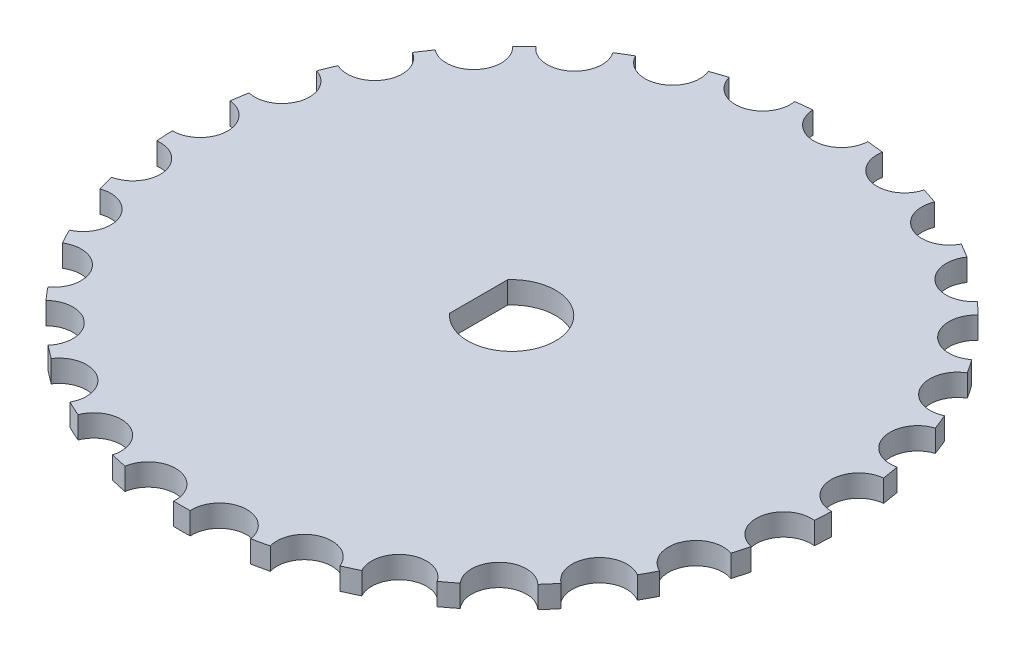
SolidWorks part; units mm, degrees
ref_plane "Front Plane" through (0, 0, 0) normal (0, 0, 1) x (1, 0, 0)
ref_plane "Top Plane" through (0, 0, 0) normal (0, 1, 0) x (1, 0, 0)
ref_plane "Right Plane" through (0, 0, 0) normal (1, 0, 0) x (0, 0, -1)
sketch "Sketch1" plane through (0, 0, 0) normal (0, 1, 0) x (1, 0, 0)
  circle A0 centre (0, 0) radius 30
  dimension "D1" = 60
extrude "Boss-Extrude1" add sketch "Sketch1" along normal blind 2
sketch "Sketch4" plane through (0, 2, 0) normal (0, 1, 0) x (1, 0, 0)
  line L0 (-3, -2.6458) -> (-3, 2.6458)
  arc A0 (-3, -2.6458) -> (-3, 2.6458) centre (0, 0) ccw
  dimension "D1" = 8
  dimension "D2" = 3
extrude "Cut-Extrude2" cut sketch "Sketch4" against normal through all
sketch "Sketch2" plane through (0, 2, 0) normal (0, 1, 0) x (1, 0, 0)
  circle A0 centre (0, 30) radius 2.5
  circle A1 centre (0, 0) radius 30 construction
  circle A2 centre (6.4491, 29.2986) radius 2.5
  circle A3 centre (12.5967, 27.2273) radius 2.5
  circle A4 centre (18.1552, 23.8828) radius 2.5
  circle A5 centre (22.8649, 19.4216) radius 2.5
  circle A6 centre (26.5054, 14.0523) radius 2.5
  circle A7 centre (28.9065, 8.0259) radius 2.5
  circle A8 centre (29.956, 1.6242) radius 2.5
  circle A9 centre (29.6048, -4.8535) radius 2.5
  circle A10 centre (27.8693, -11.1041) radius 2.5
  circle A11 centre (24.8307, -16.8356) radius 2.5
  circle A12 centre (20.631, -21.7799) radius 2.5
  circle A13 centre (15.4666, -25.7057) radius 2.5
  circle A14 centre (9.579, -28.4296) radius 2.5
  circle A15 centre (3.2436, -29.8241) radius 2.5
  circle A16 centre (-3.2436, -29.8241) radius 2.5
  circle A17 centre (-9.579, -28.4296) radius 2.5
  circle A18 centre (-15.4666, -25.7057) radius 2.5
  circle A19 centre (-20.631, -21.7799) radius 2.5
  circle A20 centre (-24.8307, -16.8356) radius 2.5
  circle A21 centre (-27.8693, -11.1041) radius 2.5
  circle A22 centre (-29.6048, -4.8535) radius 2.5
  circle A23 centre (-29.956, 1.6242) radius 2.5
  circle A24 centre (-28.9065, 8.0259) radius 2.5
  circle A25 centre (-26.5054, 14.0523) radius 2.5
  circle A26 centre (-22.8649, 19.4216) radius 2.5
  circle A27 centre (-18.1552, 23.8828) radius 2.5
  circle A28 centre (-12.5967, 27.2273) radius 2.5
  circle A29 centre (-6.4491, 29.2986) radius 2.5
  dimension "D1" = 5
  dimension "D2" = 29
extrude "Cut-Extrude1" cut sketch "Sketch2" against normal through all
